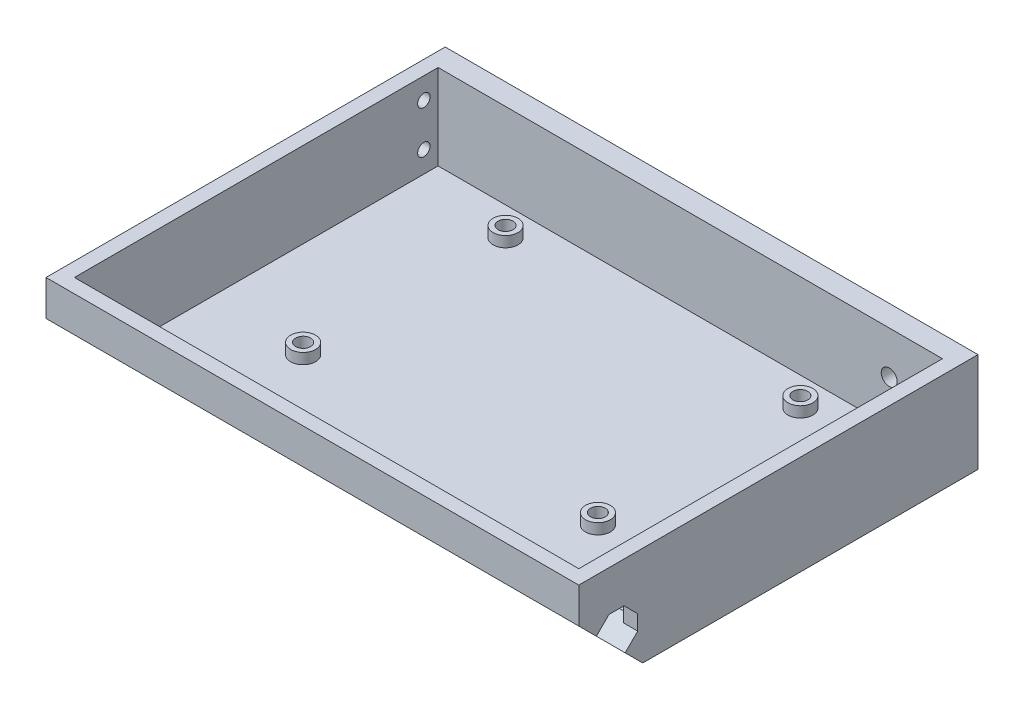
SolidWorks part; units mm, degrees
ref_plane "Front Plane" through (0, 0, 0) normal (0, 0, 1) x (1, 0, 0)
ref_plane "Top Plane" through (0, 0, 0) normal (0, 1, 0) x (1, 0, 0)
ref_plane "Right Plane" through (0, 0, 0) normal (1, 0, 0) x (0, 0, -1)
sketch "Sketch1" plane through (0, 0, 0) normal (1, 0, 0) x (0, 0, -1)
  line L1 (-14, 14) -> (14, 14)
  line L2 (-14, 14) -> (-14, -14)
  line L3 (-14, -14) -> (14, -14)
  line L4 (14, 14) -> (14, -14)
  line L5 (-14, 14) -> (14, -14) construction
  line L6 (-14, -14) -> (14, 14) construction
  point P0 (0, 0)
  dimension "D1" = 28
  dimension "D2" = 28
extrude "Boss-Extrude1" add sketch "Sketch1" along normal blind 120 and the other way blind 30
chamfer "Chamfer1" distance 18 angle 45 1 edges at (45, -14, 14)
sketch "Sketch2" plane through (0, 0, -14) normal (0, 0, -1) x (-1, 0, 0)
  line L4 (30, -14) -> (30, 14)
  line L5 (30, 14) -> (-120, 14)
  line L6 (-120, 14) -> (-120, -14)
  line L7 (-120, -14) -> (30, -14)
  line L8 (30, -14) -> (30, 14)
  line L9 (30, 14) -> (-120, 14)
  line L10 (-120, 14) -> (-120, -14)
  line L11 (-120, -14) -> (30, -14)
  dimension "D1" = 0
extrude "Boss-Extrude2" add sketch "Sketch2" along normal blind 100
sketch "Sketch3" plane through (0, 14, 0) normal (0, 1, 0) x (1, 0, 0)
  line L0 (-30, 114) -> (-30, -14) construction
  line L1 (-26, 110) -> (116, 110)
  line L2 (-26, 110) -> (-26, 10)
  line L3 (-26, 10) -> (116, 10)
  line L4 (116, 110) -> (116, 10)
  dimension "D1" = 4
  dimension "D2" = 4
  dimension "D3" = 4
  dimension "D4" = 100
extrude "Cut-Extrude1" cut sketch "Sketch3" against normal blind 24
sketch "Sketch4" plane through (0, 14, 0) normal (0, 1, 0) x (1, 0, 0)
  line L1 (-26, 10) -> (116, 10)
  line L2 (-26, 10) -> (-26, -10)
  line L3 (-26, -10) -> (116, -10)
  line L4 (116, 10) -> (116, -10)
  dimension "D1" = 4
  dimension "D2" = 4
extrude "Cut-Extrude2" cut sketch "Sketch4" against normal blind 4
chamfer "Chamfer2" distance 20 angle 45 1 edges at (45, 10, -10)
sketch "Sketch6" plane through (0, -5, 5) normal (0, -0.7071, 0.7071) x (1, 0, 0)
  line L0 (-30, 12.7279) -> (120, 12.7279) construction
  line L1 (120, 12.7279) -> (120, -12.7279) construction
  circle A0 centre (34, 10) radius 1.75
  circle A1 centre (17.9966, 10) radius 1.75
  circle A2 centre (56, 10) radius 1.75
  circle A3 centre (72, 10) radius 1.75
  circle A4 centre (72, -10) radius 1.75
  circle A5 centre (56, -10) radius 1.75
  circle A6 centre (34, -10) radius 1.75
  circle A7 centre (17.9966, -10) radius 1.75
  point P28 (45, 12.7279)
  point P31 (120, 0)
  dimension "D1" = 3.5
  dimension "D2" = 16
  dimension "D3" = 22
  dimension "D4" = 16.0034
  dimension "D5" = 20
  dimension "D6" = 11
  dimension "D7" = 10
extrude "Cut-Extrude3" cut sketch "Sketch6" against normal through all
sketch "Sketch10" plane through (0, 14, 0) normal (0, 1, 0) x (1, 0, 0)
  line L0 (-79.4783, 98.3833) -> (131.5217, 98.3833) construction
  line L1 (135.0296, 124.2015) -> (-30, 124.2015)
  line L2 (135.0296, 124.2015) -> (135.0296, 98.3833)
  line L3 (135.0296, 98.3833) -> (-30, 98.3833)
  line L4 (-30, 124.2015) -> (-30, 98.3833)
  line L5 (-30, 114) -> (-30, -14) construction
extrude "Cut-Extrude7" cut sketch "Sketch10" against normal through all
sketch "Sketch11" plane through (-30, 0, 0) normal (-1, 0, 0) x (0, 0, 1)
  line L0 (9.0503, -0.9497) -> (3.3934, 4.7071)
  line L1 (-4, -14) -> (14, 4) construction
  line L2 (3.3934, 4.7071) -> (-4.7071, -3.3934)
  line L3 (-4.7071, -3.3934) -> (0.9497, -9.0503)
  line L4 (0.9497, -9.0503) -> (9.0503, -0.9497)
  dimension "D1" = 7
  dimension "D2" = 7
  dimension "D3" = 8
extrude "Cut-Extrude8" cut sketch "Sketch11" against normal through all
chamfer "Chamfer3" distance 3 angle 45 2 edges at (-28, 4.7071, 3.3934) (-28, -3.3934, -4.7071)
sketch "Sketch12" plane through (0, -5, 5) normal (0, -0.7071, 0.7071) x (-1, 0, 0)
  line L0 (-120, -5.7279) -> (30, -5.7279) construction
  line L1 (26, -5.7279) -> (-116, -5.7279)
  line L2 (26, -5.7279) -> (26, 5.7279)
  line L3 (26, 5.7279) -> (-116, 5.7279)
  line L4 (-116, -5.7279) -> (-116, 5.7279)
  line L5 (-120, 5.7279) -> (30, 5.7279) construction
  dimension "D1" = 4
  dimension "D2" = 4
extrude "Cut-Extrude9" cut sketch "Sketch12" against normal through all
sketch "Sketch13" plane through (0, -10, 0) normal (0, 1, 0) x (1, 0, 0)
  line L0 (116, 10) -> (116, 98.3833) construction
  line L1 (-26, 98.3833) -> (116, 98.3833)
  line L2 (-26, 98.3833) -> (-26, 92.3833)
  line L3 (-26, 92.3833) -> (116, 92.3833)
  line L4 (116, 98.3833) -> (116, 92.3833)
  dimension "D1" = 6
extrude "Boss-Extrude4" add sketch "Sketch13" along normal up to surface (24 mm away) up to face at (45, 14, -43.1916)
sketch "Sketch14" plane through (0, 0, -98.3833) normal (0, 0, -1) x (-1, 0, 0)
  circle A0 centre (-101, 2) radius 2.25
  dimension "D2" = 4.5
  dimension "D1" = 131
  dimension "D3" = 16
extrude "Cut-Extrude10" cut sketch "Sketch14" against normal blind 6
sketch "Sketch15" plane through (-26, 0, 0) normal (1, 0, 0) x (0, 0, -1)
  circle A0 centre (88.3833, 8) radius 1.75
  circle A1 centre (88.3833, -4) radius 1.75
  dimension "D2" = 3.5
  dimension "D1" = 12
  dimension "D3" = 10
  dimension "D4" = 10
extrude "Cut-Extrude11" cut sketch "Sketch15" against normal through all
sketch "Sketch17" plane through (0, -10, 0) normal (0, 1, 0) x (1, 0, 0)
  circle A0 centre (1, 84.3833) radius 3.5
  circle A1 centre (84, 84.3833) radius 3.5
  circle A2 centre (84, 27.3833) radius 3.5
  circle A3 centre (1, 27.3833) radius 3.5
  dimension "D1" = 7
  dimension "D4" = 32
  dimension "D2" = 57
  dimension "D3" = 83
  dimension "D5" = 8
extrude "Boss-Extrude5" add sketch "Sketch17" along normal blind 3
sketch "Sketch18" plane through (0, -7, 0) normal (0, 1, 0) x (1, 0, 0)
  circle A0 centre (84, 84.3833) radius 2.1
  circle A1 centre (84, 27.3833) radius 2.1
  circle A2 centre (1, 27.3833) radius 2.1
  circle A3 centre (1, 84.3833) radius 2.1
  dimension "D1" = 4.2
extrude "Cut-Extrude12" cut sketch "Sketch18" against normal blind 6
